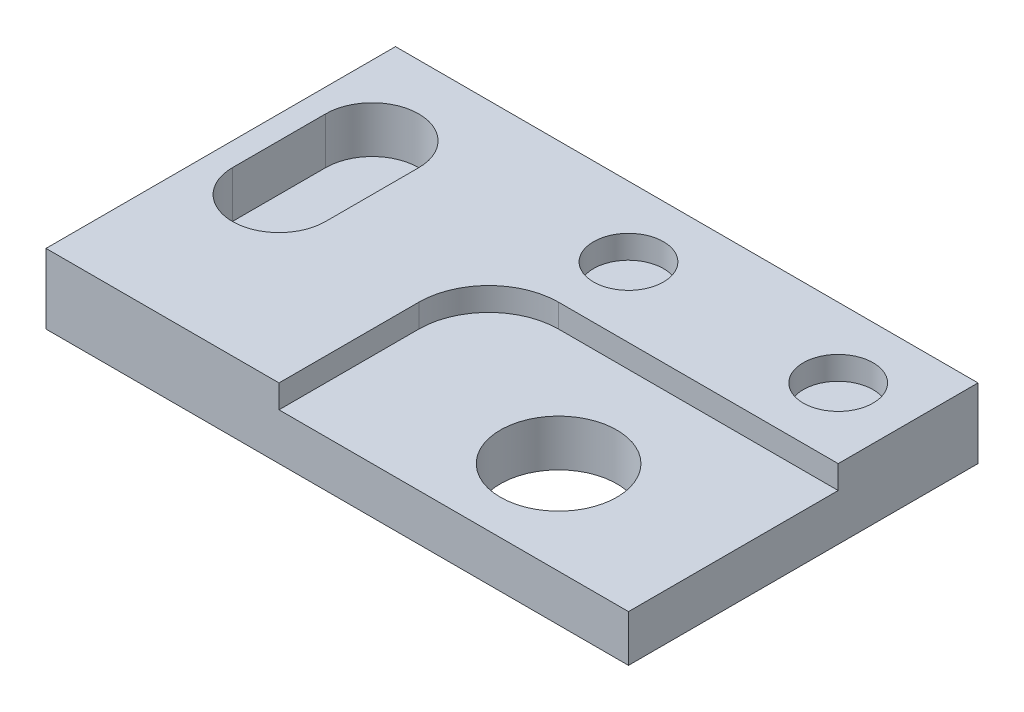
SolidWorks part; units mm, degrees
ref_plane "Front Plane" through (0, 0, 0) normal (0, 0, 1) x (1, 0, 0)
ref_plane "Top Plane" through (0, 0, 0) normal (0, 1, 0) x (1, 0, 0)
ref_plane "Right Plane" through (0, 0, 0) normal (1, 0, 0) x (0, 0, -1)
sketch "Sketch2" plane through (0, 0, 0) normal (0, 1, 0) x (1, 0, 0)
  line L1 (-125, 75) -> (125, 75)
  line L2 (-125, 75) -> (-125, -75)
  line L3 (-125, -75) -> (125, -75)
  line L4 (125, 75) -> (125, -75)
  line L5 (-125, 75) -> (125, -75) construction
  line L6 (-125, -75) -> (125, 75) construction
  point P0 (0, 0)
  dimension "D1" = 150
  dimension "D2" = 250
extrude "Boss-Extrude1" add sketch "Sketch2" against normal blind 30
sketch "Sketch3" plane through (0, 0, 0) normal (0, 1, 0) x (1, 0, 0)
  line L0 (-95, 35) -> (-95, -5) construction
  line L1 (-75, 35) -> (-75, -5)
  line L2 (-115, 35) -> (-115, -5)
  line L3 (-125, 75) -> (-125, -75) construction
  line L4 (125, 75) -> (-125, 75) construction
  line L5 (125, -75) -> (125, 75) construction
  line L7 (125, -75) -> (-25, -75)
  line L8 (125, -75) -> (125, 15)
  line L9 (125, 15) -> (5, 15)
  line L10 (-25, -75) -> (-25, -15)
  arc A0 (-75, 35) -> (-115, 35) centre (-95, 35) ccw
  arc A1 (-115, -5) -> (-75, -5) centre (-95, -5) ccw
  circle A2 centre (5, 45) radius 15
  circle A3 centre (95, 45) radius 15
  arc A4 (5, 15) -> (-25, -15) centre (5, -15) ccw
  circle A5 centre (55, -35) radius 25
  point P2 (-95, 15)
  point P24 (-25, 15)
  point P29 (51.0469, 15)
  line M10 (125, -75) -> (125, 75)
  line M13 (-125, -75) -> (125, -75)
  dimension "D1" = 20
  dimension "D5" = 30
  dimension "D6" = 30
  dimension "D13" = 30
  dimension "D14" = 50
  dimension "D2" = 10
  dimension "D3" = 60
  dimension "D4" = 40
  dimension "D7" = 30
  dimension "D8" = 90
  dimension "D9" = 30
  dimension "D10" = 30
  dimension "D11" = 90
  dimension "D12" = 150
  dimension "D15" = 80
  dimension "D16" = 50
extrude "Cut-Extrude2" cut sketch "Sketch3" against normal blind 20 contours L2 A1 L1 A0 | L2 A1 L1 A0 region at (-95, 0, -15)
extrude "Cut-Extrude3" cut sketch "Sketch3<5>" against normal blind 10 contours A2 | A3 region at (5, 0, -45) region at (95, 0, -45)
sketch "Sketch3<5>" plane through (0, 0, 0) normal (0, 1, 0) x (1, 0, 0) same geometry as "Sketch3"
extrude "Cut-Extrude4" cut sketch "Sketch3<6>" against normal through all contours A5 region at (55, 0, 35)
sketch "Sketch3<6>" plane through (0, 0, 0) normal (0, 1, 0) x (1, 0, 0) same geometry as "Sketch3"
extrude "Cut-Extrude5" cut sketch "Sketch3<7>" against normal blind 10 contours L9 A4 L10 A5 M13 M10 region at (50, 0, 73.2507)
sketch "Sketch3<7>" plane through (0, 0, 0) normal (0, 1, 0) x (1, 0, 0) same geometry as "Sketch3"
